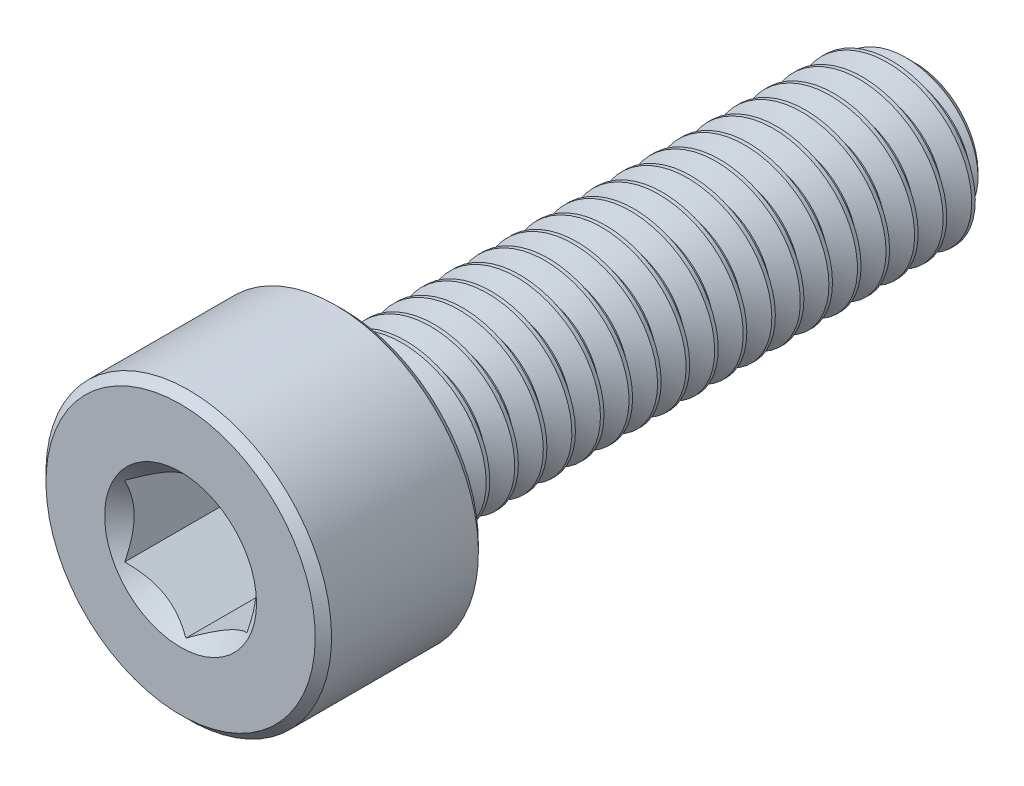
SolidWorks part; units mm, degrees
ref_plane "Front Plane" through (0, 0, 0) normal (0, 0, 1) x (1, 0, 0)
ref_plane "Top Plane" through (0, 0, 0) normal (0, 1, 0) x (1, 0, 0)
ref_plane "Right Plane" through (0, 0, 0) normal (1, 0, 0) x (0, 0, -1)
sketch "Sketch1" plane through (0, 0, 0) normal (1, 0, 0) x (0, 0, -1)
  line L0 (-9, 0) -> (9, 0) construction
  line L1 (9, 0) -> (9, 1.5453) construction
  line L2 (9, 1.5453) -> (8.5453, 2) construction
  line L3 (8.5453, 2) -> (8.475, 2) construction
  line L4 (8.475, 2) -> (-5, 2) construction
  line L5 (-5, 2) -> (-5, 3.5) construction
  line L6 (-5, 3.5) -> (-9, 3.5) construction
  line L7 (-9, 3.5) -> (-9, 0) construction
  line L8 (9, 1.5453) -> (9, 2) construction
  line L9 (8.9562, 2.0758) -> (9.3063, 1.4696) construction
  line L10 (9.3063, 1.4696) -> (9.6562, 2.0758) construction
  line L11 (9.6562, 2.0758) -> (8.9562, 2.0758) construction
  line L12 (9.3063, 2.0758) -> (9.3063, 2) construction
  line L13 (9.3063, 1.4696) -> (9.3063, 1.5453) construction
  line L14 (9.2625, 1.5453) -> (9.35, 1.5453) construction
  line L15 (9, 2) -> (9.6125, 2) construction
  line L16 (8.9781, 2.0379) -> (9.6344, 2.0379) construction
  line L17 (9, 0) -> (9, -2) construction
  line L18 (-5.2, 3.5) -> (-5, 3.3) construction
  line L19 (-8.8, 3.5) -> (-9, 3.3) construction
  line L20 (-5, 2) -> (-5, 0) construction
  line L21 (-5, 1) -> (-0.3333, 1) construction
  line L22 (-0.3333, 1) -> (4.3333, 1) construction
  line L23 (4.3333, 1) -> (9, 1) construction
  line L24 (-0.3333, 1) -> (-0.3333, 2) construction
  line L25 (-0.3333, 2) -> (-0.3333, 3.5) construction
  line L26 (4.3333, 1) -> (4.3333, 3.5) construction
  point P0 (-9, 1.5)
  point P3 (7.25, 2)
  point P4 (0, 0)
  point P18 (4.3333, 2)
  point P22 (9.3063, 1.5453)
  point P24 (8.475, 2)
  point P25 (9.3063, 2)
  point P28 (9.3063, 2.0379)
  point P29 (7.25, -2)
  point P30 (-0.3333, 2)
  point P31 (-7, 3.5)
  point P37 (-5.7, 3.5)
  point P38 (-8.7, 3.5)
  point P45 (-0.3333, 1)
  point P46 (4.3333, 1)
  dimension "D2" = 0.0875
  dimension "D7" = 0.2
  dimension "D8" = 0.2
  dimension "D9" = 0.2
  dimension "D10" = 0.1
  dimension "D11" = 0.5
  dimension "Drive Size" = 3
  dimension "Head Diameter" = 7
  dimension "Head Height" = 4
  dimension "Thread Pitch" = 0.7
  dimension "Thread Dia" = 4
  dimension "Length" = 14
  dimension "D12" = 0.525
  dimension "D4" = 1.75
  dimension "D3" = 45
sketch "Sketch2" plane through (0, 0, 0) normal (1, 0, 0) x (0, 0, -1)
  line L0 (-9, 0) -> (-9, 3.3)
  line L1 (-8.8, 3.5) -> (-5.2, 3.5)
  line L2 (-5, 3.3) -> (-5, 2.2)
  line L4 (8.5453, 2) -> (9, 1.5453)
  line L5 (9, 1.5453) -> (9, 0)
  line L6 (-5, 3.5) -> (-9, 3.5) construction
  line L7 (9, 0) -> (-9, 0)
  line L8 (-8.8, 3.5) -> (-9, 3.3) construction
  line L10 (-8.8, 3.5) -> (-9, 3.3)
  line L14 (-5.2, 3.5) -> (-5, 3.3) construction
  line L16 (-5.2, 3.5) -> (-5, 3.3)
  line L17 (-5, 2) -> (-5, 3.5) construction
  line L19 (-4.8, 2) -> (8.5453, 2)
  line L20 (8.475, 2) -> (-5, 2) construction
  arc A1 (-5, 2.2) -> (-4.8, 2) centre (-4.8, 2.2) ccw
  dimension "D3" = 0.2
revolve "Revolve1" add sketch "Sketch2" angle 360 about L7
sketch "Sketch3" plane through (0, 0, 9) normal (0, 0, 1) x (1, 0, 0)
  line L1 (1.5, -0.866) -> (1.5, 0.866)
  line L2 (1.5, 0.866) -> (0, 1.7321)
  line L3 (0, 1.7321) -> (-1.5, 0.866)
  line L4 (-1.5, 0.866) -> (-1.5, -0.866)
  line L5 (-1.5, -0.866) -> (0, -1.7321)
  line L6 (0, -1.7321) -> (1.5, -0.866)
  circle A0 centre (0, 0) radius 1.5 construction
  circle A1 centre (0, 0) radius 3.5 construction
  circle A2 centre (0, 0) radius 3.5 construction
  circle A3 centre (0, 0) radius 1.7321 construction
  point P13 (0, 0)
  dimension "D1" = 3.4641
extrude "Cut-Extrude1" cut sketch "Sketch3" against normal offset from surface (3 mm away) 1 up to face at (0, 3.3, 5)
sketch "Sketch4" plane through (0, 0, 9) normal (0, 0, 1) x (1, 0, 0)
  circle A0 centre (0, 0) radius 1.862
  dimension "D1" = 3.7239
extrude "Cut-Extrude2" cut sketch "Sketch4" against normal up to vertex (2 mm away) draft 45 up to point (0, 3.5, 7)
sketch "Sketch11" plane through (0, 0, 0) normal (1, 0, 0) x (0, 0, -1)
  line L0 (-9, 0) -> (9, 0) construction
  line L1 (-9, 0) -> (9, 0) construction
  line L2 (-2.375, 0) -> (-2.375, 2) construction
  line L3 (8.475, 2) -> (-5, 2) construction
  line L4 (6.375, 0) -> (6.375, 2) construction
  line L6 (9, 1.5453) -> (9, 2) construction
  point P2 (-2.375, 0)
  point P3 (6.375, 0)
  dimension "D1" = 2.625
  dimension "D2" = 2.625
sketch "Sketch6" plane through (0, 0, -9) normal (0, 0, -1) x (-1, 0, 0)
  circle A0 centre (0, 0) radius 2
curve "Helix/Spiral1" pitch 0.7 height 14.7 radius 2 centre (0, 0, -9) axis (0, 0, 1) start towards (0, 1, 0)
sketch "Sketch10" plane through (0, 0, 0) normal (1, 0, 0) x (0, 0, -1)
  line L0 (-4.8, -3.5) -> (-4.8, 3.5)
  line L5 (-9, 0) -> (9, 0) construction
  line L6 (-4.8, 2) -> (-4.8, -2) construction
  point P3 (-4.8, 0)
split "Split1" trim tools "Sketch10" bodies to split 106 resulting bodies 114 115
sketch "Sketch7" plane through (0, 0, 0) normal (1, 0, 0) x (0, 0, -1)
  line L0 (8.9781, 2.0379) -> (9.6344, 2.0379)
  line L1 (9.6344, 2.0379) -> (9.35, 1.5453)
  line L2 (9.35, 1.5453) -> (9.2625, 1.5453)
  line L3 (9.2625, 1.5453) -> (8.9781, 2.0379)
sweep "Cut-Sweep1" cut profiles "Sketch7" path "Helix/Spiral1" align with end faces yes
sketch "Sketch8" plane through (0, 0, 0) normal (1, 0, 0) x (0, 0, -1)
  line L0 (-5, 0) -> (-5, 2)
  line L1 (-4.8, -2) -> (-4.8, 2) construction
  line L2 (-5, 2) -> (-4.8, 2)
  line L4 (-4.8, 2) -> (-3.6453, 0)
  line L5 (-3.6453, 0) -> (-5, 0)
  line L6 (8.475, 2) -> (-5, 2) construction
  line L7 (-9, 0) -> (9, 0) construction
  dimension "D1" = 60
revolve "Revolve2" add sketch "Sketch8" angle 360 about L5
equation "\"D2@Sketch1\" = \"Thread Pitch@Sketch1\" / 8"
equation "\"D4@Helix/Spiral1\" = \"Thread Pitch@Sketch1\""
equation "\"D7@Sketch1\" = \"Head Height@Sketch1\" * .05"
equation "\"D8@Sketch1\"=\"D7@Sketch1\""
equation "\"D9@Sketch1\"=\"D7@Sketch1\""
equation "\"D10@Sketch1\"=\"D7@Sketch1\"/2"
equation "\"D11@Sketch1\"=\"D10@Sketch1\"*5"
equation "\"D4@Sketch1\"=\"Thread Pitch@Sketch1\"*2.5"
equation "\"D12@Sketch1\"=\"Thread Pitch@Sketch1\"*.75"
equation "\"D3@Helix/Spiral1\"=\"Length@Sketch1\"+\"Thread Pitch@Sketch1\""
equation "\"D3@Sketch2\"=\"Thread Dia@Sketch1\"*0.05"
equation "\"D1@Sketch11\"=\"Length@Sketch1\"*0.1875"
equation "\"D2@Sketch11\"=\"D1@Sketch11\""
equation "\"D1@Sketch4\"=\"D1@Sketch3\"*1.075"
